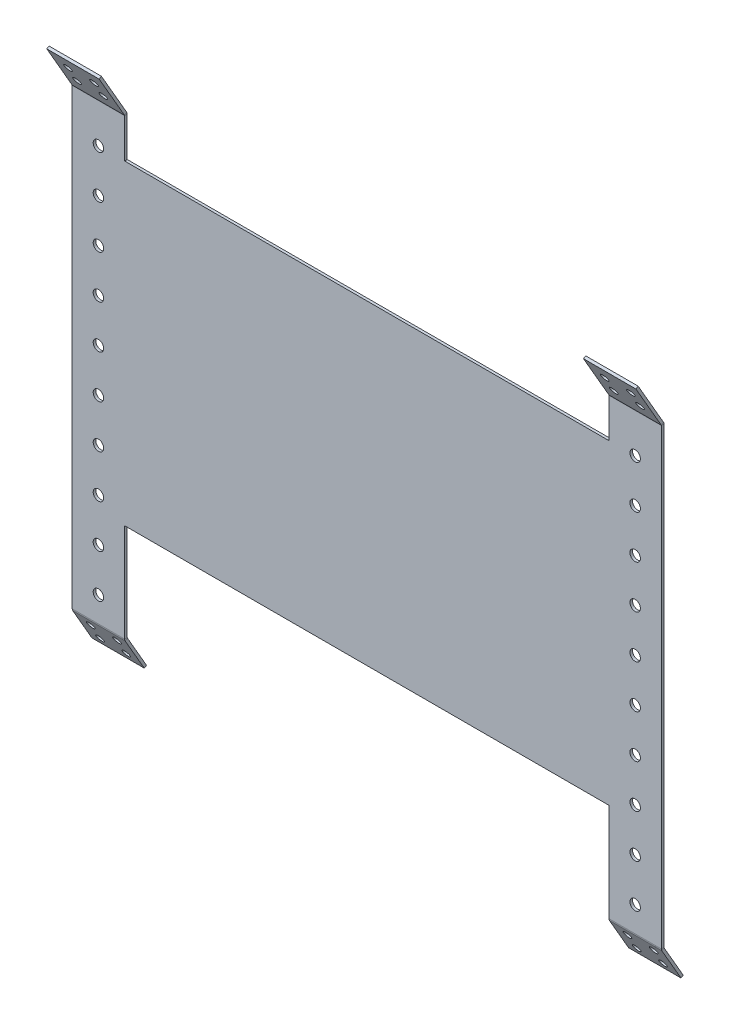
SolidWorks part; units mm, degrees
note: The reader was unsure of these and kept them because the rebuilt part matched: flange length of "Edge-Flange1", "Edge-Flange2".
ref_plane "Front Plane" through (0, 0, 0) normal (0, 0, 1) x (1, 0, 0)
ref_plane "Top Plane" through (0, 0, 0) normal (0, 1, 0) x (1, 0, 0)
ref_plane "Right Plane" through (0, 0, 0) normal (1, 0, 0) x (0, 0, -1)
sketch "Sketch1" plane through (0, 0, 0) normal (0, 0, 1) x (1, 0, 0)
  line L0 (-225, 173.125) -> (-225, -173.125)
  line L5 (225, 173.125) -> (225, -173.125)
  line L7 (-225, -173.125) -> (-185, -173.125)
  line L8 (-185, -173.125) -> (-185, -98.125)
  line L9 (-185, -98.125) -> (185, -98.125)
  line L10 (185, -98.125) -> (185, -173.125)
  line L11 (185, -173.125) -> (225, -173.125)
  line L12 (-225, 173.125) -> (-185, 173.125)
  line L13 (-185, 173.125) -> (-185, 143.125)
  line L14 (-185, 143.125) -> (185, 143.125)
  line L15 (185, 143.125) -> (185, 173.125)
  line L16 (185, 173.125) -> (225, 173.125)
  point P0 (0, 143.125)
  point P2 (-225, 303.0531)
  point P3 (0, -98.125)
  point P12 (0, 0)
  point P17 (0, 0)
  point P18 (0, 0)
  point P19 (225, 292.6991)
  point P20 (-162.5, 222.4779)
  point P21 (-162.5, -220.6482)
  point P22 (-225, 0)
  dimension "D1" = 450
  dimension "D2" = 40
  dimension "D3" = 450
  dimension "D4" = 30
  dimension "D5" = 75
  dimension "D6" = 75
  dimension "D7" = 346.25
base flange "Base-Flange1" sketch "Sketch1" thickness 2 reverse thickness direction no parameters "D1"=0.8
edge flange "Edge-Flange1" sketch "Sketch18" flange profiles "Sketch18", "Sketch19" flange angle 150 flange length 39.49 flange position bend outside bend radius 0.8 thickness 2 parameters "D6"=10, "D8"=1
sketch "Sketch18" plane through (0, 173.125, 0) normal (0, -0.5, 0.866) x (1, 0, 0)
  line L2 (-225, 0) -> (-225, 38.9541)
  line L3 (-225, 38.9541) -> (-185, 38.9541)
  line L4 (-185, 38.9541) -> (-185, 0)
  line L5 (-185, 0) -> (-225, 0) construction
  line L6 (-185, 0) -> (-225, 0)
sketch "Sketch19" plane through (0, 173.125, 0) normal (0, -0.5, 0.866) x (1, 0, 0)
  line L0 (225, 0) -> (185, 0) construction
  line L1 (225, 0) -> (185, 0)
  line L2 (225, 0) -> (225, 38.9541)
  line L3 (225, 38.9541) -> (185, 38.9541)
  line L4 (185, 38.9541) -> (185, 0)
bend "EdgeBend1" bend radius 0.8 bend angle 30 parameters "D5"=1
bend "EdgeBend2" bend radius 0.8 bend angle 30 parameters "D5"=2
edge flange "Edge-Flange2" sketch "Sketch26" flange profiles "Sketch26", "Sketch27" flange angle 150 flange length 30 flange position bend outside bend radius 0.8 thickness 2 parameters "D6"=10, "D8"=1
sketch "Sketch26" plane through (0, -173.125, -2) normal (0, 0.5, -0.866) x (1, 0, 0)
  line L2 (-225, 0) -> (-225, 29.4641)
  line L3 (-225, 29.4641) -> (-185, 29.4641)
  line L4 (-185, 29.4641) -> (-185, 0)
  line L5 (-185, 0) -> (-225, 0) construction
  line L6 (-185, 0) -> (-225, 0)
sketch "Sketch27" plane through (0, -173.125, -2) normal (0, 0.5, -0.866) x (1, 0, 0)
  line L2 (185, 0) -> (185, 29.4641)
  line L3 (185, 29.4641) -> (225, 29.4641)
  line L4 (225, 29.4641) -> (225, 0)
  line L5 (225, 0) -> (185, 0) construction
  line L6 (225, 0) -> (185, 0)
bend "EdgeBend5" bend radius 0.8 bend angle 30 parameters "D5"=3
bend "EdgeBend6" bend radius 0.8 bend angle 30 parameters "D5"=4
sketch "Sketch28" plane through (0, 0, 0) normal (0, 0, 1) x (1, 0, 0)
  line L0 (-185, 173.125) -> (-225, 173.125) construction
  line L1 (0, 143.125) -> (0, -98.125) construction
  line L2 (185, 143.125) -> (-185, 143.125) construction
  line L3 (-185, -98.125) -> (185, -98.125) construction
  circle A0 centre (-205, 143.125) radius 4
  circle A1 centre (-205, 110.125) radius 4
  circle A2 centre (-205, 77.125) radius 4
  circle A3 centre (-205, 44.125) radius 4
  circle A4 centre (-205, 11.125) radius 4
  circle A5 centre (-205, -21.875) radius 4
  circle A6 centre (-205, -54.875) radius 4
  circle A7 centre (-205, -87.875) radius 4
  circle A8 centre (-205, -120.875) radius 4
  circle A9 centre (-205, -153.875) radius 4
  circle A10 centre (205, -153.875) radius 4
  circle A11 centre (205, -120.875) radius 4
  circle A12 centre (205, -87.875) radius 4
  circle A13 centre (205, -54.875) radius 4
  circle A14 centre (205, -21.875) radius 4
  circle A15 centre (205, 11.125) radius 4
  circle A16 centre (205, 44.125) radius 4
  circle A17 centre (205, 77.125) radius 4
  circle A18 centre (205, 110.125) radius 4
  circle A19 centre (205, 143.125) radius 4
  point P4 (-205, 173.125)
  dimension "D1" = 8
  dimension "D3" = 33
  dimension "D2" = 10
extrude "Cut-Extrude1" cut sketch "Sketch28" against normal blind 2
sketch "Sketch29" plane through (0, -43.4688, 75.2902) normal (0, -0.5, 0.866) x (1, 0, 0)
  line L0 (-205, -151.3306) -> (-205, -180.5804) construction
  line L1 (-185, -151.3306) -> (-225, -151.3306) construction
  line L2 (-185, -180.5804) -> (-225, -180.5804) construction
  line L3 (-205, -165.9555) -> (-225, -165.9555) construction
  line L4 (-225, -180.5804) -> (-225, -151.3306) construction
  line L5 (-205, -151.3306) -> (-225, -151.3306) construction
  line L6 (0, 0) -> (0, -180.5804) construction
  line L7 (0, 0) -> (339.0815, 0) construction
  circle A0 centre (-215, -158.9555) radius 3
  circle A2 centre (-215, -172.9555) radius 3
  circle A3 centre (-195, -172.9555) radius 3
  circle A4 centre (-195, -158.9555) radius 3
  circle A5 centre (195, -172.9555) radius 3
  circle A6 centre (195, -158.9555) radius 3
  circle A7 centre (215, -158.9555) radius 3
  circle A8 centre (215, -172.9555) radius 3
  point P14 (-215, -151.3306)
  dimension "D1" = 6
  dimension "D2" = 7
  dimension "D3" = 7
extrude "Cut-Extrude2" cut sketch "Sketch29" against normal blind 2
sketch "Sketch30" plane through (0, 44.3348, -76.7902) normal (0, 0.5, -0.866) x (-1, 0, 0)
  line L0 (-205, 152.5948) -> (-205, 186.8062) construction
  line L1 (-205, 169.7005) -> (-214.9204, 169.7005) construction
  line L4 (-225, 189.0704) -> (-185, 189.0704) construction
  line L5 (-185, 189.0704) -> (-185, 150.3306) construction
  line L6 (-205, 189.0704) -> (-225, 189.0704) construction
  line L7 (0, 0) -> (0, 215.8422) construction
  circle A0 centre (-215, 176.7005) radius 3
  circle A1 centre (-215, 162.7005) radius 3
  circle A2 centre (-195, 162.7005) radius 3
  circle A3 centre (-195, 176.7005) radius 3
  circle A4 centre (195, 162.7005) radius 3
  circle A5 centre (195, 176.7005) radius 3
  circle A6 centre (215, 176.7005) radius 3
  circle A7 centre (215, 162.7005) radius 3
  point P8 (-215, 189.0704)
  point P16 (-185, 169.7005)
  point P19 (-205, 189.0704)
  dimension "D1" = 6
  dimension "D2" = 7
  dimension "D3" = 7
extrude "Cut-Extrude3" cut sketch "Sketch30" against normal blind 2
sketch "Bend-Lines1" [suppressed] plane through (0, 0, 0) normal (0, 1, 0) x (1, 0, 0)
sketch "Bounding-Box1" [suppressed] plane through (0, 0, 0) normal (0, 1, 0) x (1, 0, 0)
sheet metal parameters "Sheet-Metal2" thickness 2 parameters "D1"=0.8
flat pattern "Flat-Pattern2" [suppressed]
sketch "Bend-Lines2" plane through (0, 0, 0) normal (0, 1, 0) x (1, 0, 0)
sketch3d "Bounding-Box2" [suppressed]
  line L0 (225, -150, 0) -> (-225, -150, 0) construction
  line L1 (225, 150, 0) -> (-225, 150, 0) construction
  line L2 (225, -150, 0) -> (225, 150, 0) construction
  line L3 (-225, -150, 0) -> (-225, 150, 0) construction
sheet metal parameters "Sheet-Metal3" thickness 2 parameters "D1"=0.8
flat pattern "Flat-Pattern2"
sketch "Bend-Lines2" plane through (0, 0, 0) normal (0, 0, 1) x (1, 0, 0)
  line L2 (225, 150.4712) -> (185, 150.4712) construction
  line L3 (-185, 150.4712) -> (-225, 150.4712) construction
  line L6 (225, 150.4712) -> (185, 150.4712) construction
  line L7 (-185, 150.4712) -> (-225, 150.4712) construction
sketch3d "Bounding-Box2" [suppressed]
  line L0 (-225, -150, 0) -> (225, -150, 0) construction
  line L1 (-225, 189.6822, 0) -> (225, 189.6822, 0) construction
  line L2 (-225, -150, 0) -> (-225, 189.6822, 0) construction
  line L3 (225, -150, 0) -> (225, 189.6822, 0) construction
bend of the flat pattern "Flatten-<EdgeBend1>1"
bend of the flat pattern "Flatten-<EdgeBend2>1"
sheet metal parameters "Sheet-Metal4" thickness 2 parameters "D1"=0.8
flat pattern "Flat-Pattern2"
sketch "Bend-Lines2" plane through (0, 0, 0) normal (0, 0, 1) x (1, 0, 0)
  line L0 (185, -173.5962) -> (225, -173.5962) construction
  line L1 (-225, -173.5962) -> (-185, -173.5962) construction
  line L2 (225, 173.5962) -> (185, 173.5962) construction
  line L3 (-185, 173.5962) -> (-225, 173.5962) construction
  line L4 (185, -173.5962) -> (225, -173.5962) construction
  line L5 (-225, -173.5962) -> (-185, -173.5962) construction
  line L6 (225, 173.5962) -> (185, 173.5962) construction
  line L7 (-185, 173.5962) -> (-225, 173.5962) construction
sketch3d "Bounding-Box2" [suppressed]
  line L0 (-225, -203.3172, 0) -> (225, -203.3172, 0) construction
  line L1 (-225, 212.8072, 0) -> (225, 212.8072, 0) construction
  line L2 (-225, -203.3172, 0) -> (-225, 212.8072, 0) construction
  line L3 (225, -203.3172, 0) -> (225, 212.8072, 0) construction
bend of the flat pattern "Flatten-<EdgeBend1>1"
bend of the flat pattern "Flatten-<EdgeBend2>1"
bend of the flat pattern "Flatten-<EdgeBend5>1"
bend of the flat pattern "Flatten-<EdgeBend6>1"
sheet metal parameters "Sheet-Metal5" thickness 2 parameters "D1"=0.8
flat pattern "Flat-Pattern2"
sketch "Bend-Lines2" plane through (0, 0, 0) normal (0, 0, 1) x (1, 0, 0)
  line L0 (185, -173.5962) -> (225, -173.5962) construction
  line L1 (-225, -173.5962) -> (-185, -173.5962) construction
  line L2 (225, 173.5962) -> (185, 173.5962) construction
  line L3 (-185, 173.5962) -> (-225, 173.5962) construction
  line L4 (185, -173.5962) -> (225, -173.5962) construction
  line L5 (-225, -173.5962) -> (-185, -173.5962) construction
  line L6 (225, 173.5962) -> (185, 173.5962) construction
  line L7 (-185, 173.5962) -> (-225, 173.5962) construction
sketch3d "Bounding-Box2" [suppressed]
  line L0 (-225, -203.3172, 0) -> (225, -203.3172, 0) construction
  line L1 (-225, 212.8072, 0) -> (225, 212.8072, 0) construction
  line L2 (-225, -203.3172, 0) -> (-225, 212.8072, 0) construction
  line L3 (225, -203.3172, 0) -> (225, 212.8072, 0) construction
bend of the flat pattern "Flatten-<EdgeBend1>1"
bend of the flat pattern "Flatten-<EdgeBend2>1"
bend of the flat pattern "Flatten-<EdgeBend5>1"
bend of the flat pattern "Flatten-<EdgeBend6>1"
sheet metal parameters "Sheet-Metal6" thickness 2 parameters "D1"=0.8
flat pattern "Flat-Pattern2"
sketch "Bend-Lines2" plane through (0, 0, 0) normal (0, 0, 1) x (1, 0, 0)
  line L0 (185, -173.5962) -> (225, -173.5962) construction
  line L1 (-225, -173.5962) -> (-185, -173.5962) construction
  line L2 (225, 173.5962) -> (185, 173.5962) construction
  line L3 (-185, 173.5962) -> (-225, 173.5962) construction
  line L4 (185, -173.5962) -> (225, -173.5962) construction
  line L5 (-225, -173.5962) -> (-185, -173.5962) construction
  line L6 (225, 173.5962) -> (185, 173.5962) construction
  line L7 (-185, 173.5962) -> (-225, 173.5962) construction
sketch3d "Bounding-Box2" [suppressed]
  line L0 (-225, -203.3172, 0) -> (225, -203.3172, 0) construction
  line L1 (-225, 212.8072, 0) -> (225, 212.8072, 0) construction
  line L2 (-225, -203.3172, 0) -> (-225, 212.8072, 0) construction
  line L3 (225, -203.3172, 0) -> (225, 212.8072, 0) construction
bend of the flat pattern "Flatten-<EdgeBend1>1"
bend of the flat pattern "Flatten-<EdgeBend2>1"
bend of the flat pattern "Flatten-<EdgeBend5>1"
bend of the flat pattern "Flatten-<EdgeBend6>1"
sheet metal parameters "Sheet-Metal7" thickness 2 parameters "D1"=0.8
flat pattern "Flat-Pattern2"
sketch "Bend-Lines2" plane through (0, 0, 0) normal (0, 0, 1) x (1, 0, 0)
  line L0 (185, -173.5962) -> (225, -173.5962) construction
  line L1 (-225, -173.5962) -> (-185, -173.5962) construction
  line L2 (225, 173.5962) -> (185, 173.5962) construction
  line L3 (-185, 173.5962) -> (-225, 173.5962) construction
  line L4 (185, -173.5962) -> (225, -173.5962) construction
  line L5 (-225, -173.5962) -> (-185, -173.5962) construction
  line L6 (225, 173.5962) -> (185, 173.5962) construction
  line L7 (-185, 173.5962) -> (-225, 173.5962) construction
sketch3d "Bounding-Box2" [suppressed]
  line L0 (-225, -203.3172, 0) -> (225, -203.3172, 0) construction
  line L1 (-225, 212.8072, 0) -> (225, 212.8072, 0) construction
  line L2 (-225, -203.3172, 0) -> (-225, 212.8072, 0) construction
  line L3 (225, -203.3172, 0) -> (225, 212.8072, 0) construction
bend of the flat pattern "Flatten-<EdgeBend1>1"
bend of the flat pattern "Flatten-<EdgeBend2>1"
bend of the flat pattern "Flatten-<EdgeBend5>1"
bend of the flat pattern "Flatten-<EdgeBend6>1"
